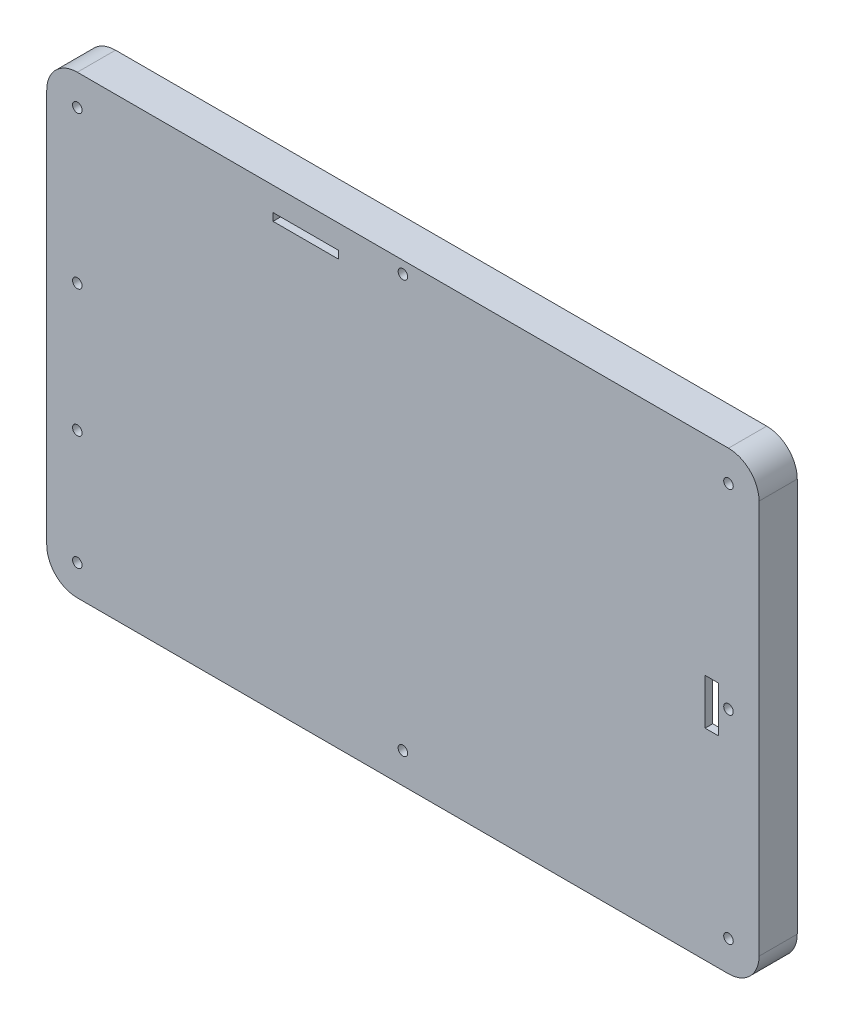
SolidWorks part; units mm, degrees
ref_plane "Front Plane" through (0, 0, 0) normal (0, 0, 1) x (1, 0, 0)
ref_plane "Top Plane" through (0, 0, 0) normal (0, 1, 0) x (1, 0, 0)
ref_plane "Right Plane" through (0, 0, 0) normal (1, 0, 0) x (0, 0, -1)
sketch "Sketch1" plane through (0, 0, 0) normal (0, 0, 1) x (1, 0, 0)
  line L0 (-89.2392, 47.2125) -> (-89.2392, -53.9075)
  line L1 (-83.1292, 39.4025) -> (73.3008, 39.4025)
  line L2 (-83.1292, 39.4025) -> (-83.1292, -49.7475)
  line L3 (-83.1292, -49.7475) -> (73.3008, -49.7475)
  line L4 (73.3008, 39.4025) -> (73.3008, -49.7475)
  line L5 (-88.7392, 46.7125) -> (76.1808, 46.7125)
  line L6 (-88.7392, 46.7125) -> (-88.7392, -53.4075)
  line L7 (-88.7392, -53.4075) -> (76.1808, -53.4075)
  line L8 (76.1808, 46.7125) -> (76.1808, -53.4075)
  line L9 (-89.2392, -53.9075) -> (76.6808, -53.9075)
  line L10 (76.6808, 47.2125) -> (76.6808, -53.9075)
  line L11 (-89.2392, 47.2125) -> (76.6808, 47.2125)
  line L12 (-98.1292, 46.4025) -> (-98.1292, -56.7475)
  line L13 (-90.1292, -64.7475) -> (80.3008, -64.7475)
  line L14 (88.3008, 46.4025) -> (88.3008, -56.7475)
  line L15 (-90.1292, 54.4025) -> (80.3008, 54.4025)
  line L16 (-98.1292, 54.4025) -> (-98.1292, -64.7475) construction
  line L17 (-98.1292, 54.4025) -> (88.3008, 54.4025) construction
  line L18 (-98.1292, -64.7475) -> (88.3008, -64.7475) construction
  line L19 (88.3008, 54.4025) -> (88.3008, -64.7475) construction
  line L21 (-21.7192, 47.2125) -> (-38.9092, 47.2125)
  line L22 (-21.7192, 47.2125) -> (-21.7192, 48.2125)
  line L23 (-21.7192, 48.2125) -> (-38.9092, 48.2125)
  line L24 (-38.9092, 47.2125) -> (-38.9092, 48.2125)
  line L25 (76.6808, -0.1475) -> (77.6808, -0.1475)
  line L26 (76.6808, -0.1475) -> (76.6808, -12.1175)
  line L27 (76.6808, -12.1175) -> (77.6808, -12.1175)
  line L28 (77.6808, -0.1475) -> (77.6808, -12.1175)
  line L29 (76.6808, -0.1475) -> (74.1808, -0.1475)
  line L30 (76.6808, -0.1475) -> (76.6808, -12.1175)
  line L31 (76.6808, -12.1175) -> (74.1808, -12.1175)
  line L32 (74.1808, -0.1475) -> (74.1808, -12.1175)
  line L33 (-38.9092, 47.2125) -> (-21.7192, 47.2125)
  line L34 (-38.9092, 47.2125) -> (-38.9092, 46.2125)
  line L35 (-38.9092, 46.2125) -> (-21.7192, 46.2125)
  line L36 (-21.7192, 47.2125) -> (-21.7192, 46.2125)
  arc A0 (-98.1292, 46.4025) -> (-90.1292, 54.4025) centre (-90.1292, 46.4025) cw
  arc A1 (-90.1292, -64.7475) -> (-98.1292, -56.7475) centre (-90.1292, -56.7475) cw
  arc A2 (88.3008, -56.7475) -> (80.3008, -64.7475) centre (80.3008, -56.7475) cw
  arc A3 (80.3008, 54.4025) -> (88.3008, 46.4025) centre (80.3008, 46.4025) cw
  circle A4 centre (80.3008, 46.4025) radius 1.25
  circle A5 centre (80.3008, -56.7475) radius 1.25
  circle A6 centre (-90.1292, -56.7475) radius 1.25
  circle A7 centre (-90.1292, 46.4025) radius 1.25
  dimension "D9" = 8
  dimension "D10" = 8
  dimension "D11" = 8
  dimension "D12" = 8
  dimension "D13" = 2.5
  dimension "D14" = 2.5
  dimension "D15" = 2.5
  dimension "D16" = 2.5
  dimension "D1" = 89.15
  dimension "D2" = 156.43
  dimension "D3" = 164.92
  dimension "D4" = 100.12
  dimension "D5" = 3.66
  dimension "D6" = 5.61
  dimension "D17" = 17.19
  dimension "D18" = 98.4
  dimension "D19" = 1
  dimension "D20" = 1
  dimension "D21" = 11.97
  dimension "D22" = 47.36
  dimension "D23" = 2.5
  dimension "D24" = 1
  dimension "D7" = 0.5
  dimension "D8" = 15
extrude "Boss-Extrude3" add sketch "Sketch1" along normal blind 2 contours A3 L15 A0 L12 A1 L13 A2 L14 A7 L11 L24 L23 L22 L10 L25 L28 L27 L9 L0 A6 A5 A4 | A7 L0 L9 L10 L31 L8 L7 L6 L5 L34 L11 | L5 L36 L35 L34 L6 L7 L8 L31 L32 L29 L1 L4 L3 L2 | L4 L1 L2 L3 | L11 L36 L5 L8 L29 L10 region at (-88.7929, 45.8545, 0) region at (27.4808, 47.1033, 0) region at (-40.8385, 46.4625, 0) region at (-4.9142, -5.1725, 0) region at (-94.2215, 50.4949, 0)
sketch "Sketch4" plane through (0, 0, 0) normal (0, 0, -1) x (-1, 0, 0)
  line L0 (21.7192, 48.2125) -> (38.9092, 48.2125) construction
  line L1 (48.2892, -39.3975) -> (-32.9108, -39.3975)
  line L2 (48.2892, -39.3975) -> (48.2892, 20.8325)
  line L3 (48.2892, 20.8325) -> (-32.9108, 20.8325)
  line L4 (-32.9108, -39.3975) -> (-32.9108, 20.8325)
  line L5 (98.1292, 46.4025) -> (98.1292, -56.7475) construction
  circle A0 centre (-30.7908, 15.5325) radius 1.15
  circle A1 centre (-30.7908, -37.0975) radius 1.15
  circle A2 centre (45.0092, -37.0975) radius 1.15
  circle A3 centre (45.0092, 15.5325) radius 1.15
  circle A4 centre (-19.6208, -30.0975) radius 1.35
  circle A5 centre (-19.6208, 14.0125) radius 1.35
  circle A6 centre (44.5092, 14.0125) radius 1.35
  circle A7 centre (44.5092, -30.0975) radius 1.35
  circle A8 centre (44.5092, 14.0125) radius 2.35
  circle A9 centre (45.0092, 15.5325) radius 2.15
  circle A10 centre (44.5092, -30.0975) radius 2.35
  circle A11 centre (45.0092, -37.0975) radius 2.15
  circle A12 centre (-30.7908, -37.0975) radius 2.15
  circle A13 centre (-19.6208, -30.0975) radius 2.35
  circle A14 centre (-19.6208, 14.0125) radius 2.35
  circle A15 centre (-30.7908, 15.5325) radius 2.15
  dimension "D1" = 2.3
  dimension "D2" = 2.3
  dimension "D3" = 2.3
  dimension "D4" = 2.3
  dimension "D5" = 2.7
  dimension "D6" = 2.7
  dimension "D7" = 2.7
  dimension "D8" = 2.7
  dimension "D9" = 64.13
  dimension "D10" = 75.8
  dimension "D11" = 0.5
  dimension "D12" = 44.11
  dimension "D13" = 51.48
  dimension "D14" = 7
  dimension "D15" = 60.23
  dimension "D16" = 81.2
  dimension "D17" = 2.12
  dimension "D18" = 2.3
  dimension "D19" = 27.38
  dimension "D20" = 49.84
  dimension "D21" = 1
extrude "Boss-Extrude4" add sketch "Sketch4" along normal blind 2 contours A11 A2 | A2 | A10 A7 | A7 | A9 A8 A6 | A9 A6 | A6 A9 | A8 A9 A6 A3 | A3 A8 | A8 A3 | A8 A9 A3 | L4 A15 A0 | A0 | L4 A15 | A14 A5 | A5 | L4 A12 | L4 A12 A1 | A1 | A4 | A13 A4 | A6 A9 A8 A3 | A3 A6 | A8 A9 A6 A3 region at (32.9228, -37.0975, 0) region at (32.8502, -37.0975, 0) region at (30.6163, 17.6146, 0) region at (32.9228, 15.5325, 0) region at (30.7908, 15.5325, 0) region at (30.7908, -37.0975, 0) region at (-45.0092, -37.0975, 0) region at (-45.049, 15.6537, 0) region at (-46.2585, 14.5244, 0) region at (-45.2794, 16.354, 0) region at (-45.3854, 16.6764, 0) region at (-44.545, 14.1214, 0) region at (-44.7929, 14.875, 0) region at (-43.4053, 15.4629, 0) region at (-46.7899, 14.1958, 0) region at (-44.2644, 13.2683, 0) region at (19.6208, -30.0975, 0) region at (19.6208, 14.0125, 0) region at (-44.5092, -30.0975, 0) region at (-42.2256, -30.0975, 0) region at (-42.92, -37.0975, 0) region at (21.9044, -30.0975, 0) region at (21.9044, 14.0125, 0)
extrude "Boss-Extrude5" add sketch "Sketch4<3>" along normal blind 2 from surface contours A2 | A7 | A9 A6 | A6 A9 | A3 A8 | A8 A3 | A5 | A0 | A1 | A4 | A3 A6 region at (30.7908, 15.5325, 0) region at (30.7908, -37.0975, 0) region at (-45.0092, -37.0975, 0) region at (-45.049, 15.6537, 0) region at (-45.2794, 16.354, 0) region at (-44.545, 14.1214, 0) region at (-44.7929, 14.875, 0) region at (-44.2644, 13.2683, 0) region at (19.6208, -30.0975, 0) region at (19.6208, 14.0125, 0) region at (-44.5092, -30.0975, 0) starting at face at (-44.7279, 14.6775, -2)
sketch "Sketch4<3>" plane through (0, 0, 0) normal (0, 0, -1) x (-1, 0, 0) same geometry as "Sketch4"
sketch "Sketch5" plane through (0, 0, 0) normal (0, 0, -1) x (-1, 0, 0)
  line L1 (-77.6808, -51.7475) -> (75.2292, -51.7475)
  line L2 (-77.6808, -51.7475) -> (-77.6808, 48.2125)
  line L3 (-77.6808, 48.2125) -> (75.2292, 48.2125)
  line L4 (75.2292, -51.7475) -> (75.2292, 48.2125)
  line L6 (90.1292, -64.7475) -> (-80.3008, -64.7475) construction
  line L7 (98.1292, 46.4025) -> (98.1292, -56.7475) construction
  line L8 (-88.3008, 46.4025) -> (-88.3008, -56.7475) construction
  line L9 (90.1292, -64.7475) -> (-80.3008, -64.7475)
  line L10 (98.1292, -56.7475) -> (98.1292, 46.4025)
  line L11 (90.1292, 54.4025) -> (-80.3008, 54.4025)
  line L12 (-88.3008, -56.7475) -> (-88.3008, 46.4025)
  line L13 (90.1292, 54.4025) -> (-80.3008, 54.4025) construction
  line L14 (-77.6808, -0.1475) -> (-77.6808, -12.1175) construction
  line L15 (21.7192, 48.2125) -> (38.9092, 48.2125) construction
  arc A0 (98.1292, -56.7475) -> (90.1292, -64.7475) centre (90.1292, -56.7475) cw
  arc A1 (-88.3008, -56.7475) -> (-80.3008, -64.7475) centre (-80.3008, -56.7475) ccw
  arc A2 (-80.3008, 54.4025) -> (-88.3008, 46.4025) centre (-80.3008, 46.4025) ccw
  arc A3 (90.1292, 54.4025) -> (98.1292, 46.4025) centre (90.1292, 46.4025) cw
  point P22 (98.1292, -64.7475)
  dimension "D3" = 8
  dimension "D4" = 8
  dimension "D5" = 8
  dimension "D6" = 8
  dimension "D1" = 13
  dimension "D2" = 22.9
extrude "Boss-Extrude6" add sketch "Sketch5" along normal blind 8
sketch "Sketch7" plane through (0, 0, -8) normal (0, 0, -1) x (-1, 0, 0)
  line L0 (75.2292, -51.7475) -> (75.2292, 48.2125) construction
  line L1 (98.1292, -18.8375) -> (75.2292, -18.8375)
  line L2 (98.1292, -18.8375) -> (98.1292, 36.4025)
  line L3 (98.1292, 36.4025) -> (75.2292, 36.4025)
  line L4 (75.2292, -18.8375) -> (75.2292, 36.4025)
  line L5 (98.1292, -56.7475) -> (98.1292, 46.4025) construction
  line L6 (90.1292, 54.4025) -> (-80.3008, 54.4025) construction
  circle A0 centre (77.8092, 33.9925) radius 1
  circle A1 centre (95.8992, 34.5025) radius 1
  circle A2 centre (77.8092, -15.7275) radius 1
  circle A3 centre (95.8992, -15.7275) radius 1
  circle A4 centre (86.3842, 12.4725) radius 1
  circle A5 centre (95.8992, -15.7275) radius 2
  circle A6 centre (77.8092, -15.7275) radius 2
  circle A7 centre (77.8092, 33.9925) radius 2
  circle A8 centre (95.8992, 34.5025) radius 2
  circle A9 centre (86.3842, 12.4725) radius 2
  line M6 (98.1292, -56.7475) -> (98.1292, 46.4025)
  line M15 (75.2292, 48.2125) -> (75.2292, -51.7475)
  dimension "D3" = 2
  dimension "D4" = 2
  dimension "D5" = 2
  dimension "D6" = 2
  dimension "D7" = 2
  dimension "D1" = 55.24
  dimension "D2" = 18
  dimension "D8" = 1.9
  dimension "D9" = 3.11
  dimension "D10" = 2.58
  dimension "D11" = 2.23
  dimension "D12" = 11.745
  dimension "D13" = 23.93
  dimension "D16" = 2.41
  dimension "D14" = 1
  dimension "D15" = 1
extrude "Cut-Extrude3" cut sketch "Sketch7" against normal blind 8 contours A8 L3 A7 L1 A6 A5 A4 M15 M6 | A6 A2 | A2 | A3 | A5 A3 | A4 | L3 A7 A0 | A0 | L3 A8 A1 | A1 | A9 A4 region at (-86.6756, 8.7259, -8) region at (-97.4739, 35.6426, -8) region at (-77.8092, 33.9925, -8) region at (-95.8992, 34.5025, -8) region at (-77.8092, -15.7275, -8) region at (-95.8992, -15.7275, -8) region at (-86.3842, 12.4725, -8) region at (-93.9557, -15.7275, -8) region at (-75.8657, -15.7275, -8) region at (-75.8657, 33.9925, -8) region at (-84.4407, 12.4725, -8)
extrude "Boss-Extrude7" add sketch "Sketch7<3>" along normal blind 2 from surface contours A2 | A6 A2 | A3 | A5 A3 | A4 | A0 | L3 A7 A0 | A1 | L3 A8 A1 | A9 A4 region at (-97.4739, 35.6426, -8) region at (-77.8092, 33.9925, -8) region at (-95.8992, 34.5025, -8) region at (-77.8092, -15.7275, -8) region at (-95.8992, -15.7275, -8) region at (-86.3842, 12.4725, -8) region at (-93.9557, -15.7275, -8) region at (-75.8657, -15.7275, -8) region at (-75.8657, 33.9925, -8) region at (-84.4407, 12.4725, -8) starting at face at (-44.7279, 14.6775, 0)
sketch "Sketch7<3>" plane through (0, 0, -8) normal (0, 0, -1) x (-1, 0, 0) same geometry as "Sketch7"
extrude "Boss-Extrude8" add sketch "Sketch7<4>" along normal blind 2 from surface contours A2 | A4 | A0 | A1 | A3 region at (-77.8092, 33.9925, -8) region at (-95.8992, 34.5025, -8) region at (-77.8092, -15.7275, -8) region at (-95.8992, -15.7275, -8) region at (-86.3842, 12.4725, -8) starting at face at (-75.8092, -15.7275, -2)
sketch "Sketch7<4>" plane through (0, 0, -8) normal (0, 0, -1) x (-1, 0, 0) same geometry as "Sketch7"
sketch "Sketch8" plane through (0, 0, 0) normal (0, 0, -1) x (-1, 0, 0)
  line L0 (98.1292, -18.8375) -> (98.1292, 36.4025) construction
  line L1 (96.1292, -18.8375) -> (98.1292, -18.8375)
  line L2 (96.1292, -18.8375) -> (96.1292, 36.4025)
  line L3 (96.1292, 36.4025) -> (98.1292, 36.4025)
  line L4 (98.1292, -18.8375) -> (98.1292, 36.4025)
  line L5 (95.2747, 36.4025) -> (75.2292, 36.4025) construction
  line L6 (98.1292, -18.8375) -> (75.2292, -18.8375) construction
  dimension "D1" = 2
extrude "Boss-Extrude9" add sketch "Sketch8" along normal blind 2
extrude "Cut-Extrude4" cut sketch "Sketch1<5>" against normal through all contours A6 | A5 | A4 | A7 region at (-90.1292, -56.7475, 0)
sketch "Sketch1<5>" plane through (0, 0, 0) normal (0, 0, 1) x (1, 0, 0) same geometry as "Sketch1"
sketch "Sketch9" plane through (0, 0, -8) normal (0, 0, -1) x (-1, 0, 0)
  line L0 (-88.3008, 46.4025) -> (-88.3008, -56.7475) construction
  line L1 (-80.3008, -64.7475) -> (90.1292, -64.7475) construction
  line L2 (90.1292, 54.4025) -> (-80.3008, 54.4025) construction
  line L3 (98.1292, 36.4025) -> (98.1292, 46.4025) construction
  line L4 (98.1292, -56.7475) -> (98.1292, -18.8375) construction
  line L5 (98.1292, -18.8375) -> (98.1292, 36.4025) construction
  circle A0 centre (-80.3008, -4.7675) radius 1.25
  circle A1 centre (4.9092, -56.7475) radius 1.25
  circle A2 centre (4.9092, 51.2525) radius 1.25
  circle A3 centre (90.1292, -26.7475) radius 1.25
  circle A4 centre (90.1292, 6.5925) radius 1.25
  dimension "D1" = 2.5
  dimension "D4" = 2.5
  dimension "D5" = 2.5
  dimension "D9" = 2.5
  dimension "D12" = 2.5
  dimension "D2" = 8
  dimension "D3" = 59.98
  dimension "D6" = 8
  dimension "D7" = 3.15
  dimension "D8" = 93.22
  dimension "D10" = 8
  dimension "D11" = 38
  dimension "D13" = 8
  dimension "D14" = 47.81
extrude "Cut-Extrude5" cut sketch "Sketch9" against normal through all
